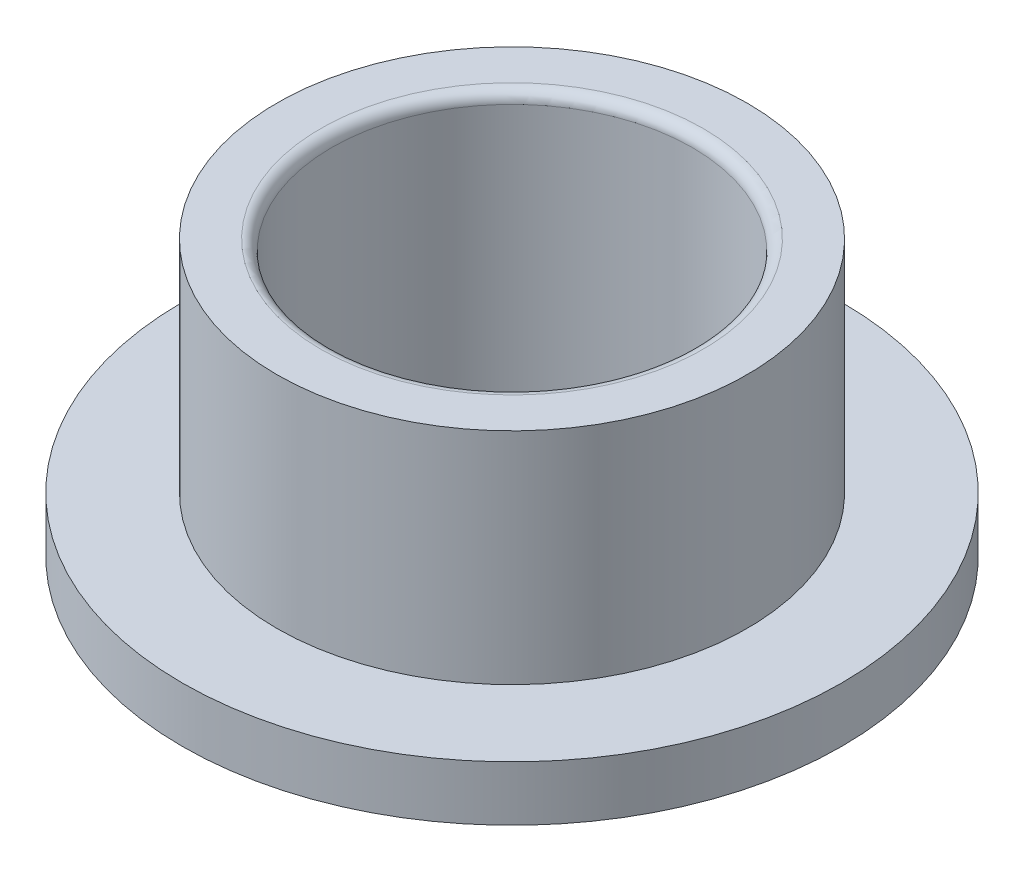
SolidWorks part; units mm, degrees
ref_plane "Front Plane" through (0, 0, 0) normal (0, 0, 1) x (1, 0, 0)
ref_plane "Top Plane" through (0, 0, 0) normal (0, 1, 0) x (1, 0, 0)
ref_plane "Right Plane" through (0, 0, 0) normal (1, 0, 0) x (0, 0, -1)
sketch "Sketch1" plane through (0, 0, 0) normal (0, 1, 0) x (1, 0, 0)
  circle A0 centre (0, 0) radius 16.4
  circle A1 centre (0, 0) radius 21.4
  dimension "D1" = 32.8
  dimension "D2" = 5
extrude "Boss-Extrude1" add sketch "Sketch1" along normal blind 20
fillet "Fillet1" radius 1 1 edges at (0, 20, 16.4)
sketch "Sketch2" plane through (0, 0, 0) normal (0, -1, 0) x (1, 0, 0)
  circle A0 centre (0, 0) radius 16.4 construction
  circle A1 centre (0, 0) radius 16.4
  circle A2 centre (0, 0) radius 30
  dimension "D1" = 60
extrude "Boss-Extrude2" add sketch "Sketch2" along normal blind 5
